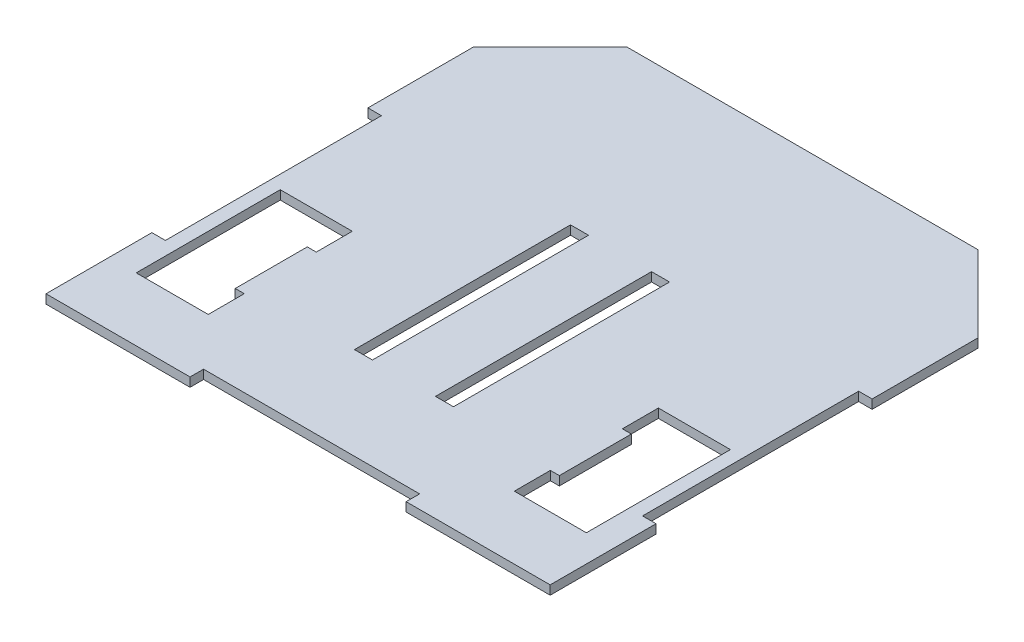
SolidWorks part; units mm, degrees
ref_plane "Front Plane" through (0, 0, 0) normal (0, 0, 1) x (1, 0, 0)
ref_plane "Top Plane" through (0, 0, 0) normal (0, 1, 0) x (1, 0, 0)
ref_plane "Right Plane" through (0, 0, 0) normal (1, 0, 0) x (0, 0, -1)
sketch "Sketch1" plane through (0, 0, 0) normal (0, 1, 0) x (1, 0, 0)
  line L0 (-177.8, 123.952) -> (-123.952, 177.8)
  line L1 (-177.8, -177.8) -> (-76.2, -177.8)
  line L2 (-177.8, -177.8) -> (-177.8, -103.124)
  line L3 (-123.952, 177.8) -> (123.952, 177.8)
  line L4 (177.8, -177.8) -> (177.8, -103.124)
  line L5 (-177.8, -177.8) -> (150.876, 150.876) construction
  line L6 (-150.876, 150.876) -> (177.8, -177.8) construction
  line L7 (0, 177.8) -> (0, -168.275) construction
  line L8 (177.8, 123.952) -> (123.952, 177.8)
  line L9 (-177.8, 49.276) -> (-168.275, 49.276)
  line L10 (177.8, 49.276) -> (168.275, 49.276)
  line L12 (177.8, -103.124) -> (168.275, -103.124)
  line L13 (168.275, 49.276) -> (168.275, -103.124)
  line L14 (-168.275, 49.276) -> (-168.275, -103.124)
  line L15 (-177.8, -103.124) -> (-168.275, -103.124)
  line L16 (177.8, 49.276) -> (177.8, 123.952)
  line L17 (-177.8, 49.276) -> (-177.8, 123.952)
  line L18 (76.2, -177.8) -> (177.8, -177.8)
  line L20 (76.2, -177.8) -> (76.2, -168.275)
  line L21 (76.2, -168.275) -> (-76.2, -168.275)
  line L22 (-76.2, -177.8) -> (-76.2, -168.275)
  point P0 (0, 0)
  point P16 (168.275, -26.924)
  point P25 (0, -168.275)
  dimension "D3" = 301.752
  dimension "D4" = 301.752
  dimension "D1" = 152.4
  dimension "D5" = 9.525
  dimension "D6" = 355.6
  dimension "D7" = 355.6
  dimension "D2" = 150.876
  dimension "D8" = 152.4
  dimension "D9" = 177.8
  dimension "D10" = 9.525
extrude "Boss-Extrude1" add sketch "Sketch1" along normal blind 6.35
sketch "Sketch4" plane through (0, 6.35, 0) normal (0, 1, 0) x (1, 0, 0)
  line L0 (158.75, -133.223) -> (158.75, -31.623)
  line L1 (158.75, -31.623) -> (120.65, -31.623)
  line L2 (120.65, -31.623) -> (120.65, -133.223)
  line L3 (120.65, -133.223) -> (158.75, -133.223)
  line L4 (177.8, -177.8) -> (-177.8, -177.8) construction
  line L5 (0, -177.8) -> (0, 177.8) construction
  line L6 (123.952, 177.8) -> (-123.952, 177.8) construction
  line L7 (-120.65, -31.623) -> (-120.65, -133.223)
  line L8 (-158.75, -31.623) -> (-120.65, -31.623)
  line L9 (-158.75, -133.223) -> (-158.75, -31.623)
  line L10 (-120.65, -133.223) -> (-158.75, -133.223)
  line L11 (-76.2, -168.275) -> (76.2, -168.275) construction
  line L15 (168.275, -103.124) -> (168.275, 49.276) construction
  dimension "D1" = 101.6
  dimension "D2" = 38.1
  dimension "D3" = 35.052
  dimension "D4" = 9.525
extrude "Cut-Extrude3" cut sketch "Sketch4" against normal through all
sketch "Sketch5" plane through (0, 6.35, 0) normal (0, 1, 0) x (1, 0, 0)
  line L0 (120.65, -133.223) -> (107.95, -133.223)
  line L1 (107.95, -133.223) -> (107.95, -107.823)
  line L2 (107.95, -107.823) -> (120.65, -107.823)
  line L3 (120.65, -31.623) -> (120.65, -133.223) construction
  line L4 (120.65, -107.823) -> (120.65, -133.223)
  line L5 (177.8, -177.8) -> (-177.8, -177.8) construction
  line L6 (0, -177.8) -> (0, 30.2394) construction
  line L7 (120.65, -31.623) -> (107.95, -31.623)
  line L8 (107.95, -31.623) -> (107.95, -57.023)
  line L9 (107.95, -57.023) -> (120.65, -57.023)
  line L10 (120.65, -57.023) -> (120.65, -31.623)
  line L11 (-107.95, -57.023) -> (-120.65, -57.023)
  line L12 (-107.95, -31.623) -> (-107.95, -57.023)
  line L13 (-120.65, -31.623) -> (-107.95, -31.623)
  line L14 (-120.65, -57.023) -> (-120.65, -31.623)
  line L15 (-107.95, -107.823) -> (-120.65, -107.823)
  line L16 (-107.95, -133.223) -> (-107.95, -107.823)
  line L17 (-120.65, -133.223) -> (-107.95, -133.223)
  line L18 (-120.65, -107.823) -> (-120.65, -133.223)
  dimension "D1" = 25.4
  dimension "D2" = 12.7
  dimension "D3" = 25.4
  dimension "D4" = 12.7
extrude "Cut-Extrude4" cut sketch "Sketch5" against normal through all
sketch "Sketch6" plane through (0, 6.35, 0) normal (0, 1, 0) x (1, 0, 0)
  line L0 (120.65, -107.823) -> (107.95, -107.823) construction
  line L1 (120.65, -57.023) -> (114.3, -57.023)
  line L2 (120.65, -57.023) -> (120.65, -107.823)
  line L3 (120.65, -107.823) -> (114.3, -107.823)
  line L4 (114.3, -57.023) -> (114.3, -107.823)
  line L5 (-120.65, -107.823) -> (-120.65, -57.023) construction
  line L6 (-120.65, -57.023) -> (-114.3, -57.023)
  line L7 (-120.65, -57.023) -> (-120.65, -107.823)
  line L8 (-120.65, -107.823) -> (-114.3, -107.823)
  line L9 (-114.3, -57.023) -> (-114.3, -107.823)
  line L10 (-107.95, -107.823) -> (-120.65, -107.823) construction
extrude "Cut-Extrude5" cut sketch "Sketch6" against normal through all
sketch "Sketch13" plane through (0, 6.35, 0) normal (0, 1, 0) x (1, 0, 0)
  line L0 (-177.8, 49.276) -> (177.8, 49.276) construction
  line L2 (-177.8, -103.124) -> (177.8, -103.124) construction
  line L3 (-34.925, 49.276) -> (-34.925, -103.124)
  line L4 (0, 49.276) -> (0, -103.124) construction
  line L5 (-34.925, 49.276) -> (-22.225, 49.276)
  line L6 (-22.225, 49.276) -> (-22.225, -103.124)
  line L7 (-22.225, -103.124) -> (-34.925, -103.124)
  line L8 (22.225, 49.276) -> (22.225, -103.124)
  line L9 (34.925, 49.276) -> (22.225, 49.276)
  line L10 (34.925, 49.276) -> (34.925, -103.124)
  line L11 (22.225, -103.124) -> (34.925, -103.124)
  dimension "D1" = 12.7
  dimension "D2" = 22.225
extrude "Cut-Extrude8" cut sketch "Sketch13" against normal through all
sketch "Bend-Lines1" [suppressed] plane through (0, 0, 0) normal (0, 1, 0) x (1, 0, 0)
sketch "Bounding-Box1" [suppressed] plane through (0, 0, 0) normal (0, 1, 0) x (1, 0, 0)
equation "\"D2@Sketch1\"=\"D3@Sketch1\"/2"
equation "\"D9@Sketch1\"=\"D6@Sketch1\"/2"
